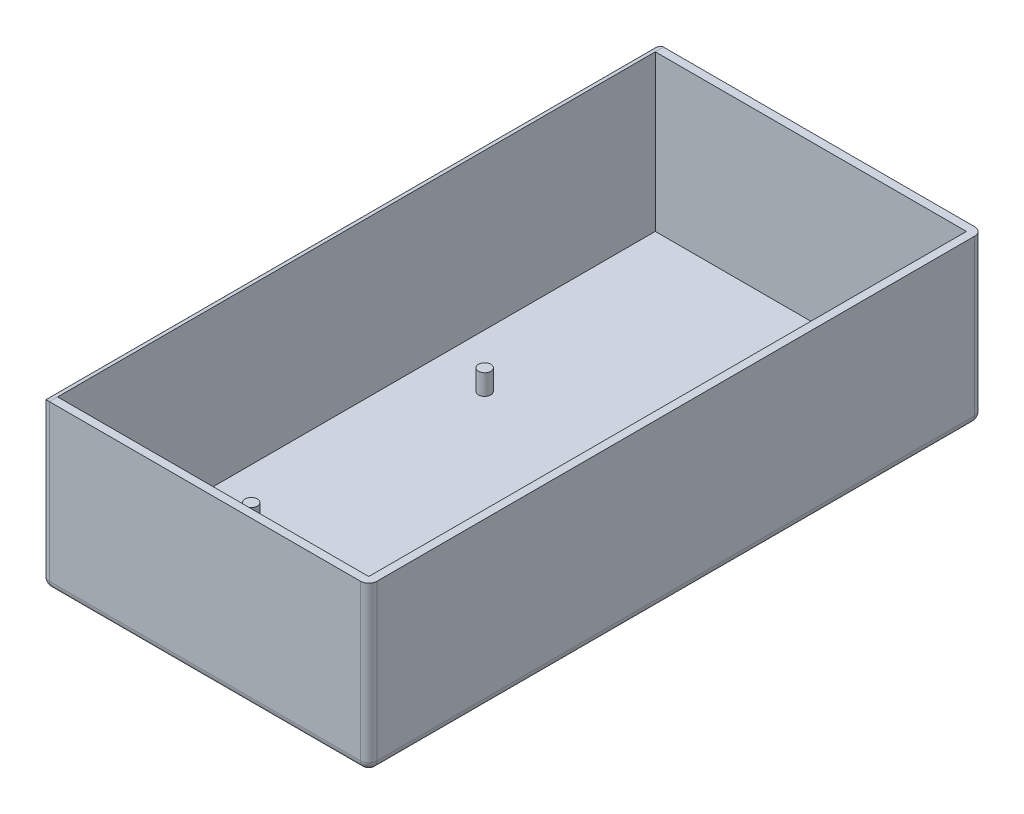
SolidWorks part; units mm, degrees
ref_plane "Front Plane" through (0, 0, 0) normal (0, 0, 1) x (1, 0, 0)
ref_plane "Top Plane" through (0, 0, 0) normal (0, 1, 0) x (1, 0, 0)
ref_plane "Right Plane" through (0, 0, 0) normal (1, 0, 0) x (0, 0, -1)
sketch "Sketch1" plane through (0, 0, 0) normal (0, 1, 0) x (1, 0, 0)
  line L1 (-48.8659, 116.7552) -> (31.1341, 116.7552)
  line L2 (-48.8659, 116.7552) -> (-48.8659, -33.2448)
  line L3 (-48.8659, -33.2448) -> (31.1341, -33.2448)
  line L4 (31.1341, 116.7552) -> (31.1341, -33.2448)
extrude "Boss-Extrude1" add sketch "Sketch1" along normal blind 40
sketch "Sketch2" plane through (0, 40, 0) normal (0, 1, 0) x (1, 0, 0)
  line L0 (-8.8659, 116.7552) -> (-8.8659, -33.2448) construction
  line L1 (31.1341, 116.7552) -> (-48.8659, 116.7552) construction
  line L2 (-48.8659, -33.2448) -> (31.1341, -33.2448) construction
  line L3 (-48.8659, 41.7552) -> (31.1341, 41.7552) construction
  line L4 (-48.8659, 116.7552) -> (-48.8659, -33.2448) construction
  line L5 (31.1341, -33.2448) -> (31.1341, 116.7552) construction
  line L7 (-46.8659, 114.7552) -> (29.1341, 114.7552)
  line L8 (-46.8659, 114.7552) -> (-46.8659, -31.2448)
  line L9 (-46.8659, -31.2448) -> (29.1341, -31.2448)
  line L10 (29.1341, 114.7552) -> (29.1341, -31.2448)
  line L11 (-46.8659, 114.7552) -> (29.1341, -31.2448) construction
  line L12 (-46.8659, -31.2448) -> (29.1341, 114.7552) construction
  point P12 (-8.8659, 41.7552)
  dimension "D1" = 2
  dimension "D2" = 2
extrude "Cut-Extrude1" cut sketch "Sketch2" against normal blind 38
sketch "Sketch4" plane through (0, 2, 0) normal (0, 1, 0) x (1, 0, 0)
  line L0 (-8.8659, 114.7552) -> (-8.8659, -35.0172) construction
  line L1 (29.1341, 114.7552) -> (-46.8659, 114.7552) construction
  line L2 (-46.8659, 41.7552) -> (29.1341, 41.7552) construction
  line L3 (-46.8659, 114.7552) -> (-46.8659, -31.2448) construction
  line L4 (29.1341, -31.2448) -> (29.1341, 114.7552) construction
  circle A0 centre (-33.8659, 60.0723) radius 1.5
  circle A1 centre (-33.8659, 3.0723) radius 1.5
  circle A2 centre (16.1341, 60.0723) radius 1.5
  circle A3 centre (16.1341, 3.0723) radius 1.5
  point P12 (-8.8659, 20.5723)
  dimension "D7" = 3
  dimension "D8" = 3
extrude "Boss-Extrude3" add sketch "Sketch4" along normal blind 5
fillet "Fillet1" radius 2 9 edges at (31.1341, 20, -116.7552) (31.1341, 0, -41.7552) (-8.8659, 0, -116.7552) (-48.8659, 40, -41.7552) (-48.8659, 20, -116.7552) (-48.8659, 0, -41.7552) (-8.8659, 0, 33.2448) (-48.8659, 20, 33.2448) (31.1341, 20, 33.2448)
